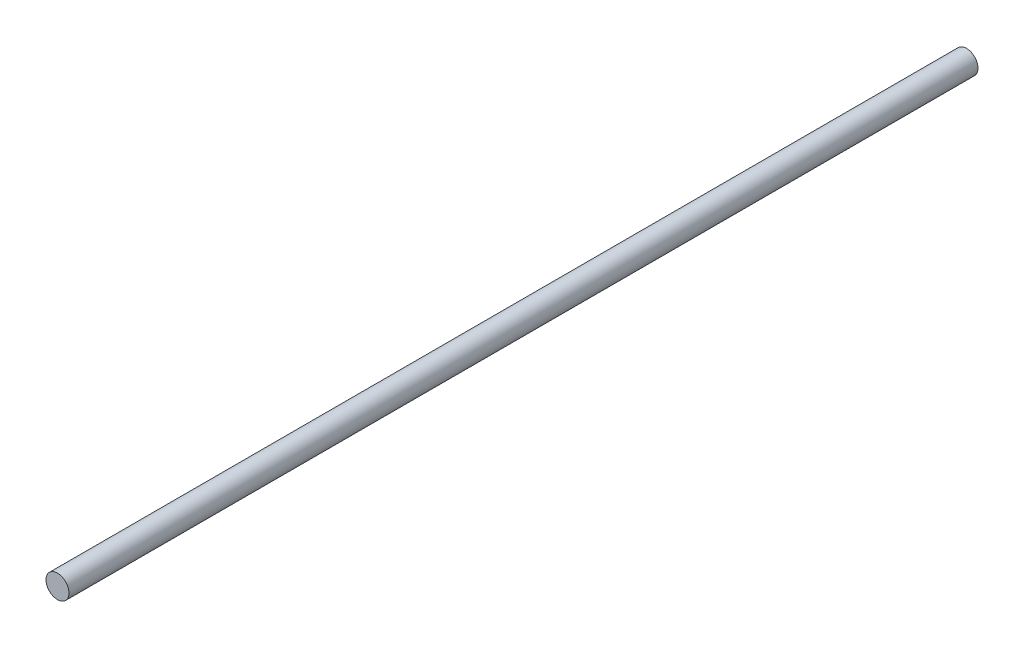
SolidWorks part; units mm, degrees
material "1023 Carbon Steel Sheet (SS)"
ref_plane "Front Plane" through (0, 0, 0) normal (1, 0, 0) x (0, 1, 0)
ref_plane "Top Plane" through (0, 0, 0) normal (0, 0, 1) x (0, 1, 0)
ref_plane "Right Plane" through (0, 0, 0) normal (0, 1, 0) x (-1, 0, 0)
sketch "Sketch1" plane through (0, 0, 0) normal (0, 0, 1) x (0, 1, 0)
  circle A0 centre (0, 0) radius 4
  dimension "D1" = 8
extrude "Boss-Extrude1" add sketch "Sketch1" along normal blind 316 contours A0 region at (0, 0, 0)
